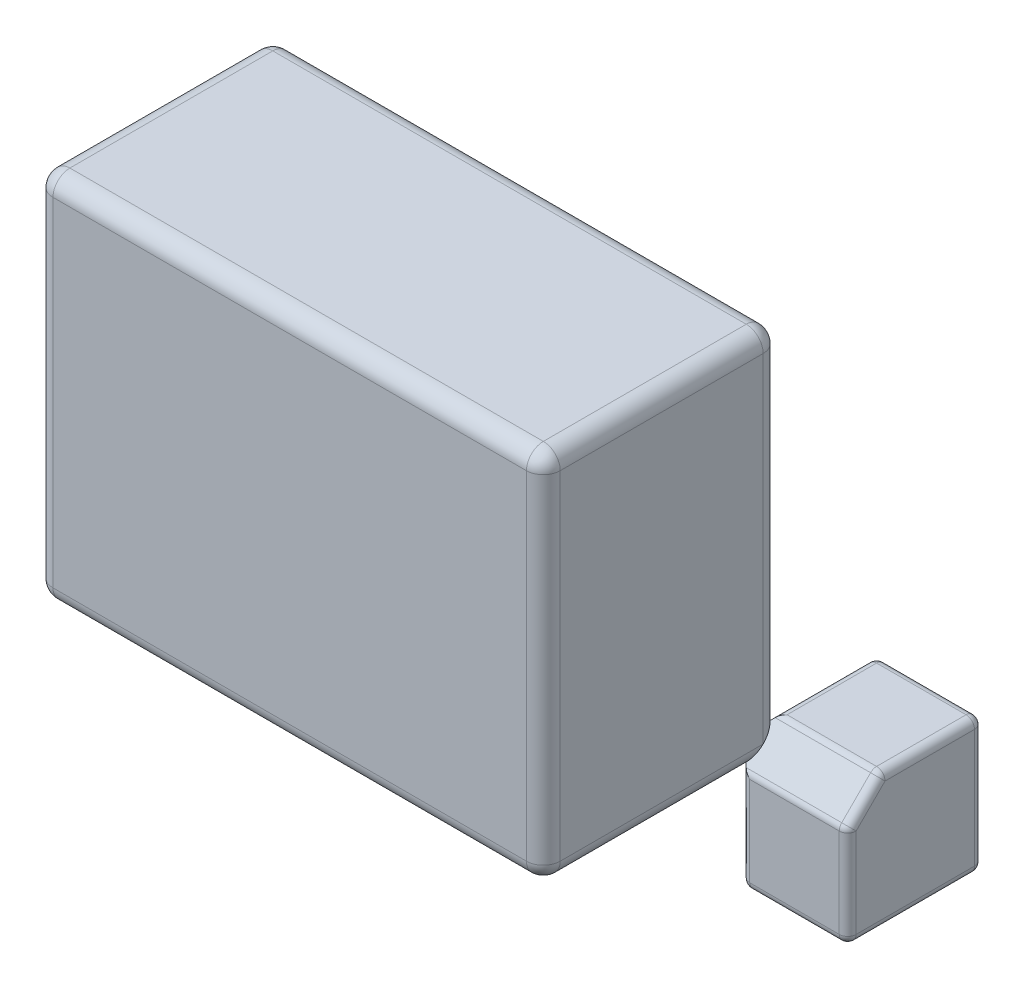
SolidWorks part; units mm, degrees
ref_plane "Front Plane" through (0, 0, 0) normal (0, 0, 1) x (1, 0, 0)
ref_plane "Top Plane" through (0, 0, 0) normal (0, 1, 0) x (1, 0, 0)
ref_plane "Right Plane" through (0, 0, 0) normal (1, 0, 0) x (0, 0, -1)
sketch "Sketch1" plane through (0, 0, 0) normal (0, 0, 1) x (1, 0, 0)
  line L1 (0, 0) -> (30, 0)
  line L2 (0, 0) -> (0, 22)
  line L3 (0, 22) -> (30, 22)
  line L4 (30, 0) -> (30, 22)
  dimension "D1" = 30
  dimension "D2" = 22
extrude "Boss-Extrude1" add sketch "Sketch1" along normal blind 14
sketch "Sketch2" plane through (0, 0, 0) normal (0, 0, -1) x (-1, 0, 0)
  line L0 (-30, 0) -> (-30, 22) construction
  line L1 (-28, 2) -> (-36, 2)
  line L2 (-28, 2) -> (-28, -6)
  line L3 (-28, -6) -> (-36, -6)
  line L4 (-36, 2) -> (-36, -6)
  line L5 (0, 0) -> (-30, 0) construction
  dimension "D1" = 2
  dimension "D2" = 2
  dimension "D3" = 8
  dimension "D4" = 8
shell "Shell1" thickness 1
extrude "Boss-Extrude3" add sketch "Sketch2" along normal blind 6 and the other way blind 2 contours L3 L4 L1 L2
chamfer "Chamfer2" distance 2 angle 45 3 edges at (33, 2, 2) (28, 2, -3) (28, -3, 2)
fillet "Fillet1" radius 1 12 edges at (0, 11, 0) (14, 0, 0) (30, 12, 0) (15, 22, 0) (15, 0, 14) (30, 11, 14) (15, 22, 14) (0, 22, 7) (30, 22, 7) (30, 0, 8) (0, 0, 7) (0, 11, 14)
fillet "Fillet2" radius 0.5 18 edges at (36, -6, -2) (32, -6, -6) (29, -6, 1) (33, -6, 2) (28, -6, -3) (28, -3, -6) (28, 0, -3) (28, -3, 0) (33, 0, 2) (29, 1, -6) (33, 2, -6) (36, 2, -3) (33, 2, 0) (30, 2, -3) (36, -3, 2) (36, -2, -6) (30, -3, 2) (36, 1, 1)
